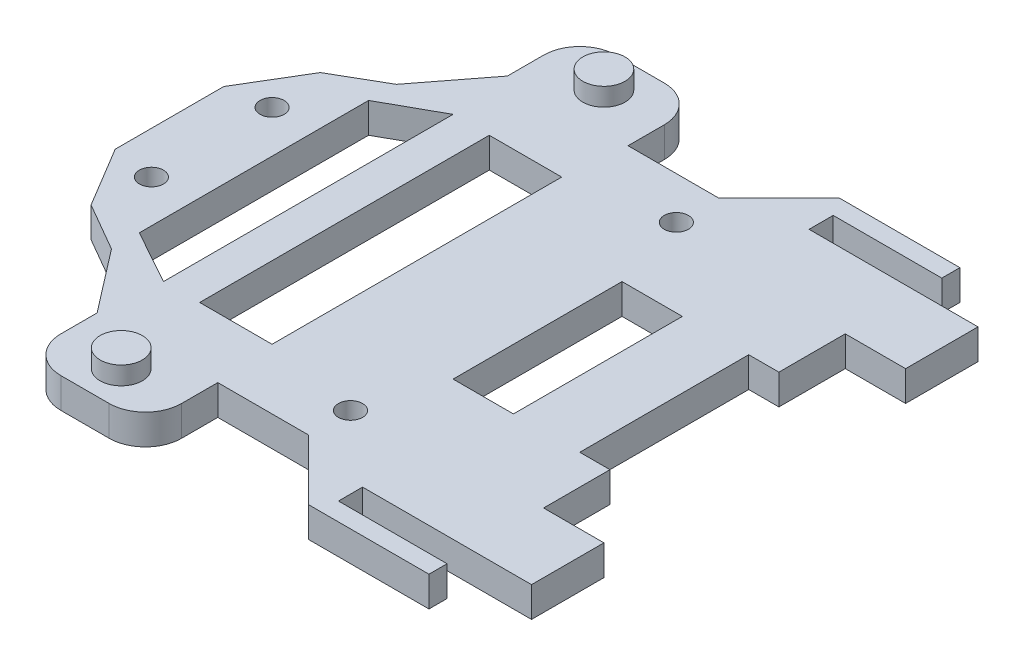
SolidWorks part; units mm, degrees
material "Plain Carbon Steel"
ref_plane "Front Plane" through (0, 0, 0) normal (0, 0, 1) x (1, 0, 0)
ref_plane "Top Plane" through (0, 0, 0) normal (0, 1, 0) x (1, 0, 0)
ref_plane "Right Plane" through (0, 0, 0) normal (1, 0, 0) x (0, 0, -1)
sketch "Sketch1" plane through (0, 0, 0) normal (0, 1, 0) x (1, 0, 0)
  line L0 (0, 0) -> (51.2308, 0) construction
  line L1 (0, -9) -> (0, 9)
  line L2 (0, 9) -> (6, 19)
  line L3 (6, 19) -> (14, 23.6188)
  line L4 (14, 23.6188) -> (22, 34)
  line L5 (22, 34) -> (22, 40)
  line L6 (28, 46) -> (36, 46)
  line L7 (42, 40) -> (42, 34)
  line L8 (42, 34) -> (57, 34)
  line L9 (57, 34) -> (67, 44)
  line L10 (67, 44) -> (87, 44)
  line L11 (87, 44) -> (87, 41)
  line L12 (87, 41) -> (69, 41)
  line L13 (69, 41) -> (69, 37)
  line L14 (69, 37) -> (97, 37)
  line L15 (97, 37) -> (97, 25)
  line L16 (97, 25) -> (87, 25)
  line L17 (87, 25) -> (87, 14)
  line L18 (87, 14) -> (82, 14)
  line L19 (82, 14) -> (82, -14)
  line L20 (61, 14) -> (71, 14)
  line L21 (71, 14) -> (71, -14)
  line L23 (61, -14) -> (61, 14)
  line L28 (14, 19) -> (23, 24)
  line L29 (23, 24) -> (23, -24)
  line L31 (14, -19) -> (14, 19)
  line L32 (14, -19) -> (23, -24)
  line L34 (61, -14) -> (71, -14)
  line L35 (87, -14) -> (82, -14)
  line L36 (87, -25) -> (87, -14)
  line L37 (97, -25) -> (87, -25)
  line L38 (97, -37) -> (97, -25)
  line L39 (69, -37) -> (97, -37)
  line L40 (69, -41) -> (69, -37)
  line L41 (87, -41) -> (69, -41)
  line L42 (87, -44) -> (87, -41)
  line L43 (67, -44) -> (87, -44)
  line L44 (57, -34) -> (67, -44)
  line L45 (42, -34) -> (57, -34)
  line L46 (42, -40) -> (42, -34)
  line L47 (28, -46) -> (36, -46)
  line L48 (22, -34) -> (22, -40)
  line L49 (14, -23.6188) -> (22, -34)
  line L50 (6, -19) -> (14, -23.6188)
  line L51 (0, -9) -> (6, -19)
  line L53 (29, 24) -> (41, 24)
  line L54 (29, 24) -> (29, -24)
  line L55 (29, -24) -> (41, -24)
  line L56 (41, 24) -> (41, -24)
  line L57 (29, 24) -> (41, -24) construction
  line L58 (29, -24) -> (41, 24) construction
  circle A6 centre (57, -27) radius 2
  circle A7 centre (32, -40) radius 3.5
  circle A8 centre (7, -10) radius 2
  circle A9 centre (57, 27) radius 2
  circle A10 centre (7, 10) radius 2
  circle A11 centre (32, 40) radius 3.5
  circle A12 centre (32, -40) radius 3.5
  arc A13 (42, -40) -> (36, -46) centre (36, -40) cw
  arc A14 (28, -46) -> (22, -40) centre (28, -40) cw
  arc A15 (36, 46) -> (42, 40) centre (36, 40) cw
  arc A16 (22, 40) -> (28, 46) centre (28, 40) cw
  point P24 (35, 0)
  point P34 (0, 0)
  point P36 (33, -39.4506)
  point P41 (82, 0)
  point P64 (87, 42.5)
  point P68 (0, 0)
  point P69 (33, -40)
  point P70 (33, -39.898)
  point P71 (0, 0)
  point P72 (0, 0)
  point P76 (42, -46)
  point P79 (22, -46)
  point P82 (42, 46)
  point P85 (22, 46)
  dimension "D28" = 20
  dimension "D31" = 4
  dimension "D34" = 40
  dimension "D36" = 38
  dimension "D30" = 4
  dimension "D39" = 6
  dimension "D35" = 7
  dimension "D40" = 7
  dimension "D2" = 6
  dimension "D3" = 8
  dimension "D4" = 8
  dimension "D5" = 20
  dimension "D6" = 15
  dimension "D7" = 10
  dimension "D8" = 18
  dimension "D9" = 4
  dimension "D10" = 30
  dimension "D11" = 88
  dimension "D12" = 74
  dimension "D13" = 28
  dimension "D14" = 50
  dimension "D15" = 5
  dimension "D16" = 11
  dimension "D17" = 92
  dimension "D18" = 12
  dimension "D19" = 10
  dimension "D20" = 9
  dimension "D21" = 59
  dimension "D22" = 135
  dimension "D23" = 10
  dimension "D24" = 48
  dimension "D25" = 12
  dimension "D26" = 30
  dimension "D27" = 41
  dimension "D29" = 80
  dimension "D32" = 18
  dimension "D33" = 10
  dimension "D37" = 27
  dimension "D38" = 55
extrude "Boss-Extrude1" add sketch "Sketch1" along normal blind 5 contours L1 L51 L50 L49 L48 L47 L46 L45 L44 L43 L42 L41 L40 L39 L38 L37 L36 L35 L19 L18 L17 L16 L15 L14 L13 L12 L11 L10 L9 L8 L7 L6 L5 L4 L3 L2 A10 L53 L56 L55 L54 L34 L23 L20 L21 L32 L31 | A11 | A7 region at (51.5635, 0, 0)
extrude "Boss-Extrude2" add sketch "Sketch1<3>" along normal blind 8 contours A7 | A11 region at (32, 0, 40) region at (32, 0, -40)
sketch "Sketch1<3>" plane through (0, 0, 0) normal (0, 1, 0) x (1, 0, 0) same geometry as "Sketch1"
